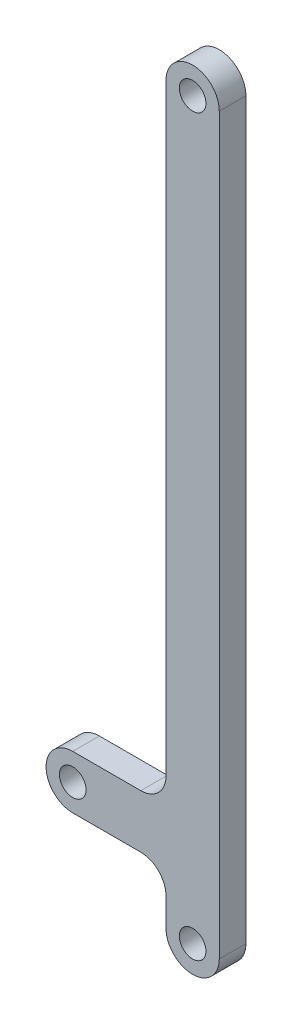
SolidWorks part; units mm, degrees
ref_plane "Front Plane" through (0, 0, 0) normal (0, 0, 1) x (1, 0, 0)
ref_plane "Top Plane" through (0, 0, 0) normal (0, 1, 0) x (1, 0, 0)
ref_plane "Right Plane" through (0, 0, 0) normal (1, 0, 0) x (0, 0, -1)
sketch "Sketch1" plane through (0, 0, 0) normal (0, 0, 1) x (1, 0, 0)
  line L0 (-47.542, -98.8825) -> (-47.542, -112.2705)
  line L2 (-47.542, 237.7295) -> (-47.542, -49.4825)
  line L4 (-22.142, 237.7295) -> (-22.142, -112.2705)
  line L5 (-59.542, -61.4825) -> (-91.992, -61.4825)
  line L7 (-59.542, -86.8825) -> (-91.992, -86.8825)
  arc A0 (-47.542, 237.7295) -> (-22.142, 237.7295) centre (-34.842, 237.7295) cw
  arc A1 (-47.542, -112.2705) -> (-22.142, -112.2705) centre (-34.842, -112.2705) ccw
  arc A2 (-91.992, -61.4825) -> (-91.992, -86.8825) centre (-91.992, -74.1825) ccw
  circle A3 centre (-34.842, 237.7295) radius 6.35
  circle A4 centre (-91.992, -74.1825) radius 6.35
  circle A5 centre (-34.842, -112.2705) radius 6.35
  arc A6 (-47.542, -98.8825) -> (-59.542, -86.8825) centre (-59.542, -98.8825) ccw
  arc A7 (-59.542, -61.4825) -> (-47.542, -49.4825) centre (-59.542, -49.4825) ccw
  point P18 (-47.542, -61.4825)
  dimension "D6" = 12.7
  dimension "D7" = 12
  dimension "D1" = 25.4
  dimension "D2" = 350
  dimension "D3" = 25.4
  dimension "D4" = 44.45
  dimension "D5" = 299.212
extrude "Boss-Extrude3" add sketch "Sketch1" along normal blind 12.7
